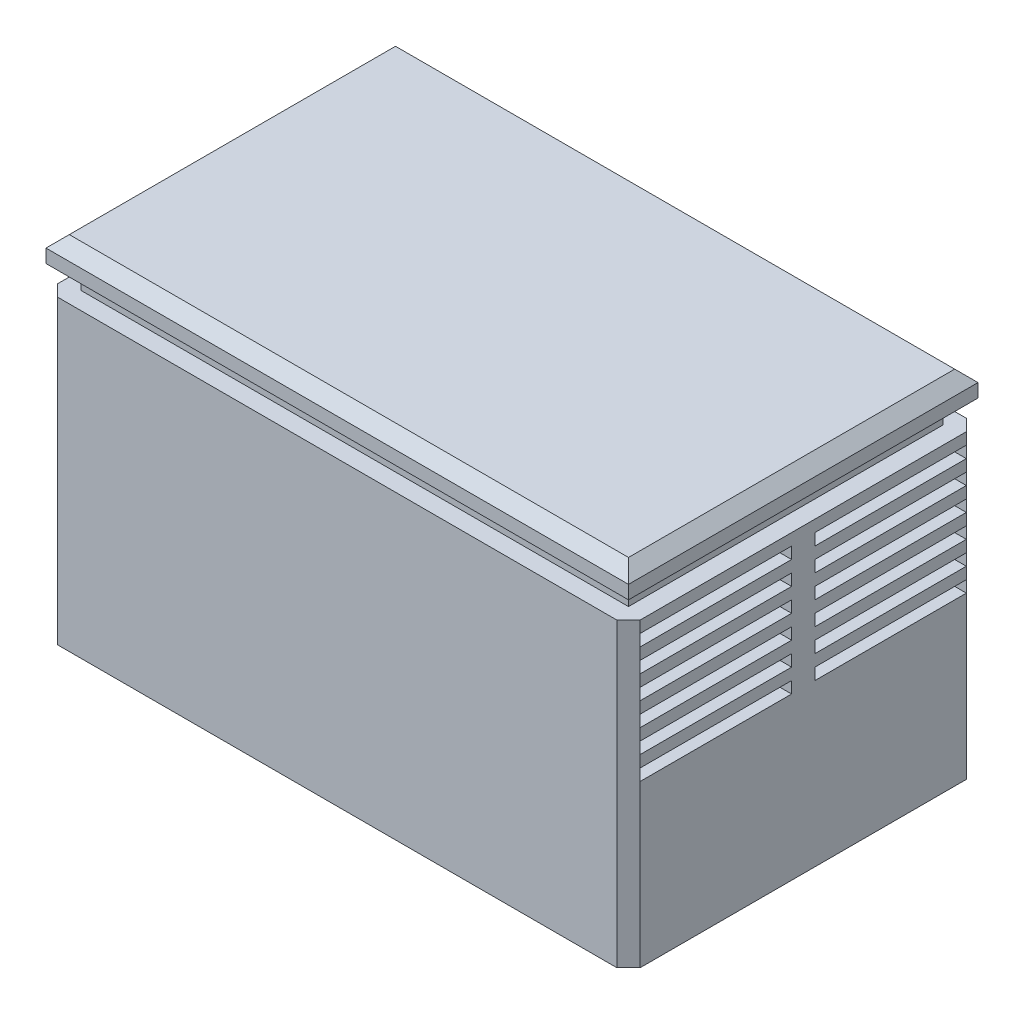
SolidWorks part; units mm, degrees
material "2024 Alloy"
ref_plane "Front Plane" through (0, 0, 0) normal (0, 0, 1) x (1, 0, 0)
ref_plane "Top Plane" through (0, 0, 0) normal (0, 1, 0) x (1, 0, 0)
ref_plane "Right Plane" through (0, 0, 0) normal (1, 0, 0) x (0, 0, -1)
sketch "Sketch1" plane through (0, 0, 0) normal (0, 0, 1) x (1, 0, 0)
  line L0 (250, 118.4806) -> (235, 118.4806)
  line L1 (250, 150) -> (-250, 150)
  line L2 (250, 150) -> (250, 118.4806)
  line L3 (250, -150) -> (-250, -150)
  line L4 (-250, 150) -> (-250, 118.4806)
  line L5 (250, 150) -> (-250, -150) construction
  line L6 (250, -150) -> (-250, 150) construction
  line L7 (235, 118.4806) -> (235, 108.4806)
  line L8 (235, 108.4806) -> (250, 108.4806)
  line L9 (-250, 118.4806) -> (-235, 118.4806)
  line L10 (-235, 118.4806) -> (-235, 108.4806)
  line L11 (-235, 108.4806) -> (-250, 108.4806)
  line L12 (250, 108.4806) -> (250, -150)
  line L13 (-250, 108.4806) -> (-250, -150)
  point P0 (0, 0)
  dimension "D1" = 500
  dimension "D2" = 300
  dimension "D3" = 10
  dimension "D4" = 15
  dimension "D5" = 15
  dimension "D6" = 10
extrude "Boss-Extrude1" add sketch "Sketch1" along normal blind 300
sketch "Sketch2" plane through (-250, 0, 0) normal (-1, 0, 0) x (0, 0, 1)
  line L0 (300, 108.4806) -> (0, 108.4806) construction
  line L1 (300, 118.4806) -> (285, 118.4806)
  line L2 (300, 118.4806) -> (300, 108.4806)
  line L3 (300, 108.4806) -> (285, 108.4806)
  line L4 (285, 118.4806) -> (285, 108.4806)
  line L6 (0, 118.4806) -> (15, 118.4806)
  line L7 (0, 118.4806) -> (0, 108.4806)
  line L8 (0, 108.4806) -> (15, 108.4806)
  line L9 (15, 118.4806) -> (15, 108.4806)
  dimension "D1" = 15
  dimension "D2" = 15
extrude "Cut-Extrude1" cut sketch "Sketch2" against normal through all
sketch "Sketch4" plane through (-250, 0, 0) normal (-1, 0, 0) x (0, 0, 1)
  line L10 (0, 108.4806) -> (0, -150) construction
  line L11 (10, 98.4806) -> (140, 98.4806)
  line L12 (10, 98.4806) -> (10, 88.4806)
  line L13 (10, 88.4806) -> (140, 88.4806)
  line L14 (140, 98.4806) -> (140, 88.4806)
  line L15 (300, 108.4806) -> (0, 108.4806) construction
  line L16 (160, 98.4806) -> (160, 88.4806)
  line L17 (160, 88.4806) -> (290, 88.4806)
  line L18 (160, 98.4806) -> (290, 98.4806)
  line L19 (290, 98.4806) -> (290, 88.4806)
  line L20 (160, 78.4806) -> (160, 68.4806)
  line L21 (160, 68.4806) -> (290, 68.4806)
  line L22 (160, 78.4806) -> (290, 78.4806)
  line L23 (290, 78.4806) -> (290, 68.4806)
  line L24 (160, 58.4806) -> (160, 48.4806)
  line L25 (160, 48.4806) -> (290, 48.4806)
  line L26 (160, 58.4806) -> (290, 58.4806)
  line L27 (290, 58.4806) -> (290, 48.4806)
  line L28 (160, 38.4806) -> (160, 28.4806)
  line L29 (160, 28.4806) -> (290, 28.4806)
  line L30 (160, 38.4806) -> (290, 38.4806)
  line L31 (290, 38.4806) -> (290, 28.4806)
  line L32 (160, 18.4806) -> (160, 8.4806)
  line L33 (160, 8.4806) -> (290, 8.4806)
  line L34 (160, 18.4806) -> (290, 18.4806)
  line L35 (290, 18.4806) -> (290, 8.4806)
  line L36 (160, -1.5194) -> (160, -11.5194)
  line L37 (160, -11.5194) -> (290, -11.5194)
  line L38 (160, -1.5194) -> (290, -1.5194)
  line L39 (290, -1.5194) -> (290, -11.5194)
  line L40 (10, 78.4806) -> (10, 68.4806)
  line L41 (10, 68.4806) -> (140, 68.4806)
  line L42 (10, 78.4806) -> (140, 78.4806)
  line L43 (140, 78.4806) -> (140, 68.4806)
  line L44 (10, 58.4806) -> (10, 48.4806)
  line L45 (10, 48.4806) -> (140, 48.4806)
  line L46 (10, 58.4806) -> (140, 58.4806)
  line L47 (140, 58.4806) -> (140, 48.4806)
  line L48 (10, 38.4806) -> (10, 28.4806)
  line L49 (10, 28.4806) -> (140, 28.4806)
  line L50 (10, 38.4806) -> (140, 38.4806)
  line L51 (140, 38.4806) -> (140, 28.4806)
  line L52 (10, 18.4806) -> (10, 8.4806)
  line L53 (10, 8.4806) -> (140, 8.4806)
  line L54 (10, 18.4806) -> (140, 18.4806)
  line L55 (140, 18.4806) -> (140, 8.4806)
  line L56 (10, -1.5194) -> (10, -11.5194)
  line L57 (10, -11.5194) -> (140, -11.5194)
  line L58 (10, -1.5194) -> (140, -1.5194)
  line L59 (140, -1.5194) -> (140, -11.5194)
  dimension "D1" = 10
  dimension "D2" = 10
  dimension "D3" = 10
  dimension "D4" = 130
  dimension "D5" = 2
  dimension "D6" = 6
extrude "Cut-Extrude2" cut sketch "Sketch4" against normal blind 30
sketch "Sketch7" plane through (250, 0, 0) normal (1, 0, 0) x (0, 0, -1)
  line L0 (-300, -150) -> (-300, 108.4806) construction
  line L1 (-290, 98.4806) -> (-160, 98.4806)
  line L2 (-290, 98.4806) -> (-290, 88.4806)
  line L3 (-290, 88.4806) -> (-160, 88.4806)
  line L4 (-160, 98.4806) -> (-160, 88.4806)
  line L5 (-285, 108.4806) -> (-15, 108.4806) construction
  line L6 (-140, 98.4806) -> (-140, 88.4806)
  line L7 (-140, 98.4806) -> (-10, 98.4806)
  line L8 (-140, 88.4806) -> (-10, 88.4806)
  line L9 (-10, 98.4806) -> (-10, 88.4806)
  line L10 (-140, 78.4806) -> (-140, 68.4806)
  line L11 (-140, 78.4806) -> (-10, 78.4806)
  line L12 (-140, 68.4806) -> (-10, 68.4806)
  line L13 (-10, 78.4806) -> (-10, 68.4806)
  line L14 (-140, 58.4806) -> (-140, 48.4806)
  line L15 (-140, 58.4806) -> (-10, 58.4806)
  line L16 (-140, 48.4806) -> (-10, 48.4806)
  line L17 (-10, 58.4806) -> (-10, 48.4806)
  line L18 (-140, 38.4806) -> (-140, 28.4806)
  line L19 (-140, 38.4806) -> (-10, 38.4806)
  line L20 (-140, 28.4806) -> (-10, 28.4806)
  line L21 (-10, 38.4806) -> (-10, 28.4806)
  line L22 (-140, 18.4806) -> (-140, 8.4806)
  line L23 (-140, 18.4806) -> (-10, 18.4806)
  line L24 (-140, 8.4806) -> (-10, 8.4806)
  line L25 (-10, 18.4806) -> (-10, 8.4806)
  line L26 (-140, -1.5194) -> (-140, -11.5194)
  line L27 (-140, -1.5194) -> (-10, -1.5194)
  line L28 (-140, -11.5194) -> (-10, -11.5194)
  line L29 (-10, -1.5194) -> (-10, -11.5194)
  line L30 (-290, 78.4806) -> (-290, 68.4806)
  line L31 (-290, 78.4806) -> (-160, 78.4806)
  line L32 (-290, 68.4806) -> (-160, 68.4806)
  line L33 (-160, 78.4806) -> (-160, 68.4806)
  line L34 (-290, 58.4806) -> (-290, 48.4806)
  line L35 (-290, 58.4806) -> (-160, 58.4806)
  line L36 (-290, 48.4806) -> (-160, 48.4806)
  line L37 (-160, 58.4806) -> (-160, 48.4806)
  line L38 (-290, 38.4806) -> (-290, 28.4806)
  line L39 (-290, 38.4806) -> (-160, 38.4806)
  line L40 (-290, 28.4806) -> (-160, 28.4806)
  line L41 (-160, 38.4806) -> (-160, 28.4806)
  line L42 (-290, 18.4806) -> (-290, 8.4806)
  line L43 (-290, 18.4806) -> (-160, 18.4806)
  line L44 (-290, 8.4806) -> (-160, 8.4806)
  line L45 (-160, 18.4806) -> (-160, 8.4806)
  line L46 (-290, -1.5194) -> (-290, -11.5194)
  line L47 (-290, -1.5194) -> (-160, -1.5194)
  line L48 (-290, -11.5194) -> (-160, -11.5194)
  line L49 (-160, -1.5194) -> (-160, -11.5194)
  dimension "D1" = 10
  dimension "D2" = 10
  dimension "D3" = 10
  dimension "D4" = 130
  dimension "D5" = 2
  dimension "D6" = 6
extrude "Cut-Extrude3" cut sketch "Sketch7" against normal blind 30
chamfer "Chamfer1" distance 10 angle 45 4 edges at (250, 150, 150) (0, 150, 300) (-250, 150, 150) (0, 150, 0)
chamfer "Chamfer2" distance 10 angle 45 4 edges at (250, 118.4806, 150) (0, 118.4806, 300) (0, 118.4806, 0) (-250, 118.4806, 150)
chamfer "Chamfer3" distance 10 angle 45 4 edges at (250, -20.7597, 300) (250, -20.7597, 0) (-250, -20.7597, 0) (-250, -20.7597, 300)
